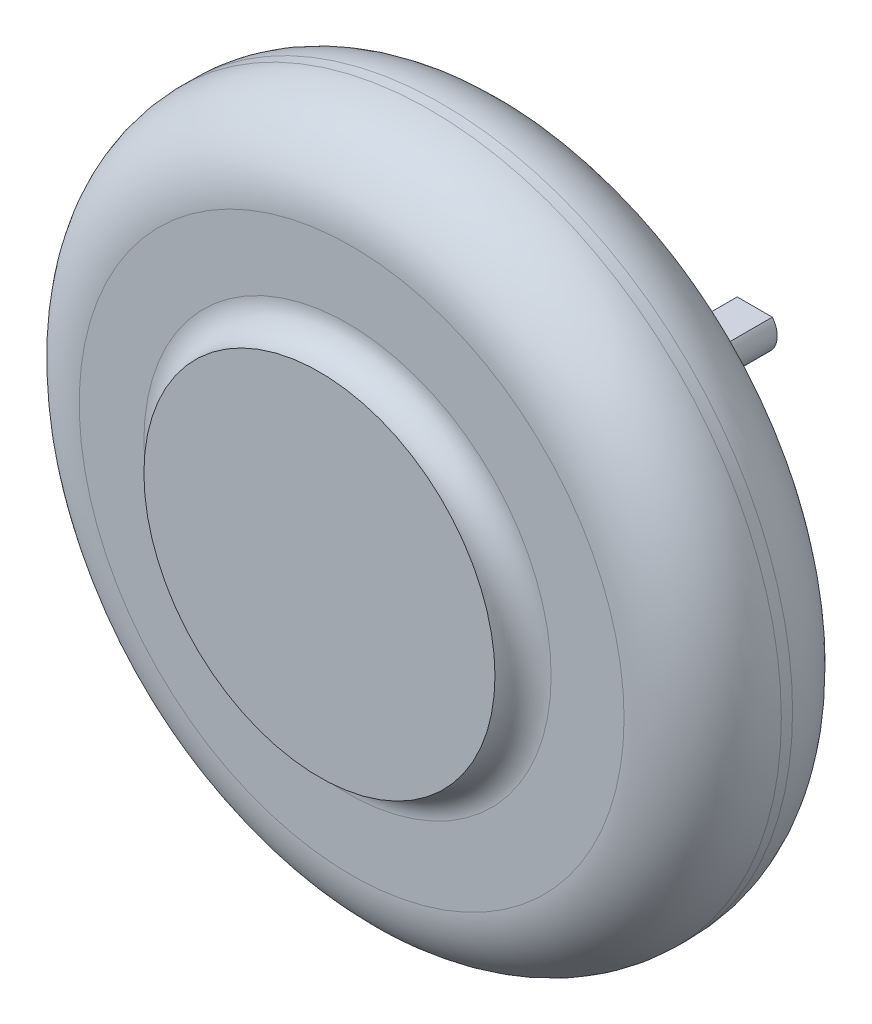
SolidWorks part; units mm, degrees
ref_plane "Piano frontale" through (0, 0, 0) normal (0, 0, 1) x (1, 0, 0)
ref_plane "Piano superiore" through (0, 0, 0) normal (0, 1, 0) x (1, 0, 0)
ref_plane "Piano destro" through (0, 0, 0) normal (1, 0, 0) x (0, 0, -1)
sketch "Schizzo1" plane through (0, 0, 0) normal (0, 0, 1) x (1, 0, 0)
  circle A0 centre (1.4631, 0) radius 125
  dimension "D1" = 250
extrude "Estrusione-Estrusione1" add sketch "Schizzo1" along normal blind 60
sketch "Schizzo2" plane through (0, 0, 60) normal (0, 0, 1) x (1, 0, 0)
  circle A0 centre (0, 0) radius 62.5
  dimension "D1" = 125
extrude "Estrusione-Estrusione2" add sketch "Schizzo2" along normal blind 10
sketch "Schizzo3" plane through (0, 0, 0) normal (0, 0, -1) x (-1, 0, 0)
  circle A0 centre (0, 0) radius 22.5
  dimension "D1" = 45
extrude "Estrusione-Estrusione3" add sketch "Schizzo3" along normal blind 15
sketch "Schizzo4" plane through (0, 0, -15) normal (0, 0, -1) x (-1, 0, 0)
  circle A0 centre (0, 0) radius 8
  dimension "D1" = 16
extrude "Estrusione-Estrusione4" add sketch "Schizzo4" along normal blind 70
fillet "Raccordo1" radius 10 2 edges at (-22.5, 0, 0) (62.5, 0, 60)
fillet "Raccordo2" radius 28 2 edges at (126.4631, 0, 0) (126.4631, 0, 60)
sketch "Schizzo5" plane through (0, 0, -85) normal (0, 0, -1) x (-1, 0, 0)
  line L0 (-6.245, 5) -> (6.245, 5)
  circle A0 centre (0, 0) radius 8 construction
  dimension "D1" = 5
extrude "Taglio-Estrusione1" cut sketch "Schizzo5" against normal blind 45 and the other way through all
